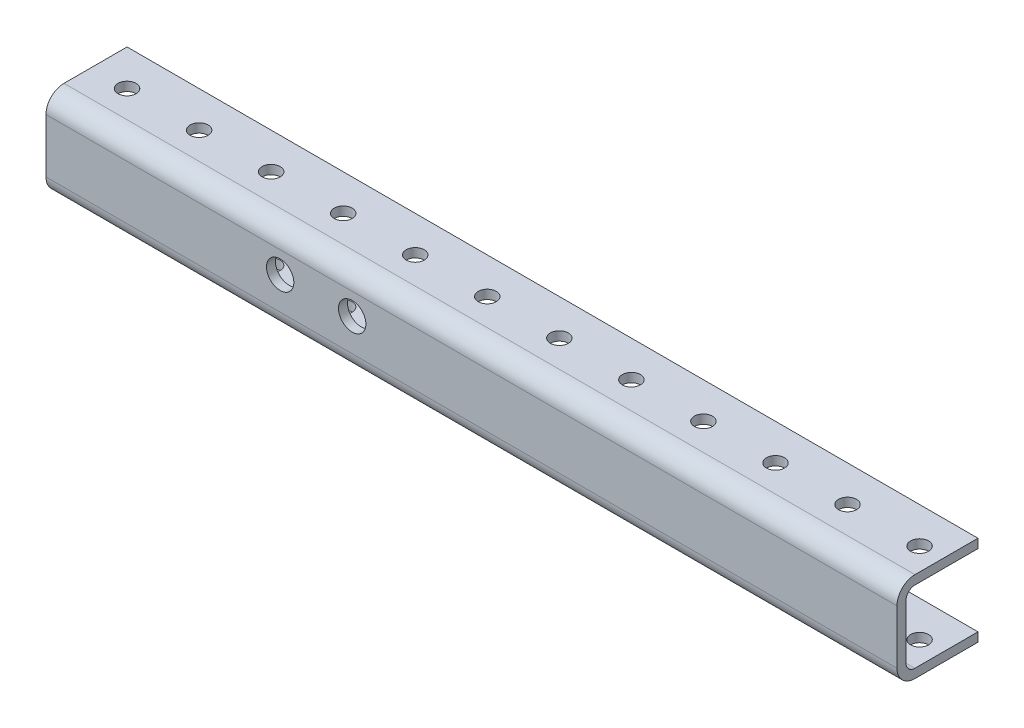
SolidWorks part; units mm, degrees
ref_plane "Front Plane" through (0, 0, 0) normal (0, 0, 1) x (1, 0, 0)
ref_plane "Top Plane" through (0, 0, 0) normal (0, 1, 0) x (1, 0, 0)
ref_plane "Right Plane" through (0, 0, 0) normal (1, 0, 0) x (0, 0, -1)
ref_plane "Plane1" through (0, 0, 3.175) normal (0, 0, 1) x (1, 0, 0)
sketch "Sketch1" plane through (0, 0, 3.175) normal (0, 0, 1) x (1, 0, 0)
  line L0 (872.98, -7.202) -> (872.98, 24.548)
  line L1 (872.98, 24.548) -> (-16.02, 24.548)
  line L2 (-16.02, 24.548) -> (-16.02, -7.202)
  line L3 (-16.02, -7.202) -> (872.98, -7.202)
extrude "Extrude1" add sketch "Sketch1" against normal blind 28.575
sketch "Sketch2" plane through (-16.02, 0, 0) normal (-1, 0, 0) x (0, 0, 1)
  line L0 (-25.4, 21.373) -> (-25.4, -4.027)
  line L1 (-25.4, -4.027) -> (0, -4.027)
  line L2 (0, -4.027) -> (0, 21.373)
  line L3 (0, 21.373) -> (-25.4, 21.373)
extrude "Extrude2" cut sketch "Sketch2" against normal up to next
hole_wizard "Hole1" positions "Sketch4" profile "Sketch3" legacy
sketch "Sketch4" plane through (0, 24.548, 0) normal (0, 1, 0) x (-1, 0, 0)
  point P0 (3.32, -12.7)
sketch "Sketch3" plane through (-3.32, 24.548, -12.7) normal (1, 0, 0) x (0, 0, 1)
  line L0 (0, 0) -> (0, 3.175)
  line L1 (0, 3.175) -> (3.175, 3.175)
  line L2 (3.175, 3.175) -> (3.175, 0)
  line L3 (3.175, 0) -> (0, 0)
  line L4 (0, 110) -> (0, -10) construction
  dimension "Diameter" = 6.35
  dimension "Depth" = 3.175
sketch3d "3DSketch1"
  point P0 (428.6664, 8.6668, -7.2024)
  point P1 (528.6664, 8.6668, -7.2024)
ref_axis "Axis1" through (528.6664, 8.6668, -7.2024) along (-1, 0, 0)
pattern_linear "LPattern1" count 35 spacing 25.4 along (1, 0, 0) of "Hole1"
hole_wizard "Hole2" positions "Sketch6" profile "Sketch5" legacy
sketch "Sketch6" plane through (0, 0, 3.175) normal (0, 0, 1) x (1, 0, 0)
  point P0 (66.53, 10.578)
sketch "Sketch5" plane through (66.53, 10.578, 3.175) normal (1, 0, 0) x (0, -1, 0)
  line L0 (0, 0) -> (0, 3.175)
  line L1 (0, 3.175) -> (4.826, 3.175)
  line L2 (4.826, 3.175) -> (4.826, 0)
  line L3 (4.826, 0) -> (0, 0)
  line L4 (0, 110) -> (0, -10) construction
  dimension "Diameter" = 9.652
  dimension "Depth" = 3.175
sketch3d "3DSketch2"
  point P0 (428.8468, 8.4517, -7.1294)
  point P1 (528.8468, 8.4517, -7.1294)
ref_axis "Axis2" through (528.8468, 8.4517, -7.1294) along (-1, 0, 0)
pattern_linear "LPattern2" count 12 spacing 25.4 along (1, 0, 0) skipping (2, 0), (3, 0), (4, 0), (5, 0), (6, 0), (7, 0), (8, 0), (9, 0) of "Hole2"
hole_wizard "Hole3" positions "Sketch8" profile "Sketch7" legacy
sketch "Sketch8" plane through (0, 0, 3.175) normal (0, 0, 1) x (1, 0, 0)
  point P0 (428.48, 6.768)
sketch "Sketch7" plane through (428.48, 6.768, 3.175) normal (1, 0, 0) x (0, -1, 0)
  line L0 (0, 0) -> (0, 3.175)
  line L1 (0, 3.175) -> (4.826, 3.175)
  line L2 (4.826, 3.175) -> (4.826, 0)
  line L3 (4.826, 0) -> (0, 0)
  line L4 (0, 110) -> (0, -10) construction
  dimension "Diameter" = 9.652
  dimension "Depth" = 3.175
hole_wizard "Hole4" positions "Sketch10" profile "Sketch9" legacy
sketch "Sketch10" plane through (0, 0, 3.175) normal (0, 0, 1) x (1, 0, 0)
  point P0 (511.03, 10.578)
sketch "Sketch9" plane through (511.03, 10.578, 3.175) normal (1, 0, 0) x (0, -1, 0)
  line L0 (0, 0) -> (0, 3.175)
  line L1 (0, 3.175) -> (4.826, 3.175)
  line L2 (4.826, 3.175) -> (4.826, 0)
  line L3 (4.826, 0) -> (0, 0)
  line L4 (0, 110) -> (0, -10) construction
  dimension "Diameter" = 9.652
  dimension "Depth" = 3.175
sketch3d "3DSketch3"
  point P0 (429.3014, 8.4448, -7.1738)
  point P1 (529.3014, 8.4448, -7.1738)
ref_axis "Axis3" through (529.3014, 8.4448, -7.1738) along (-1, 0, 0)
pattern_linear "LPattern3" count 12 spacing 25.4 along (1, 0, 0) skipping (2, 0), (3, 0), (4, 0), (5, 0), (6, 0), (7, 0), (8, 0), (9, 0) of "Hole4"
hole_wizard "Hole5" positions "Sketch12" profile "Sketch11" legacy
sketch "Sketch12" plane through (0, 0, 3.175) normal (0, 0, 1) x (1, 0, 0)
  point P0 (669.78, 8.673)
sketch "Sketch11" plane through (669.78, 8.673, 3.175) normal (1, 0, 0) x (0, -1, 0)
  line L0 (0, 0) -> (0, 3.175)
  line L1 (0, 3.175) -> (1.5875, 3.175)
  line L2 (1.5875, 3.175) -> (1.5875, 0)
  line L3 (1.5875, 0) -> (0, 0)
  line L4 (0, 110) -> (0, -10) construction
  dimension "Diameter" = 3.175
  dimension "Depth" = 3.175
hole_wizard "Hole6" positions "Sketch14" profile "Sketch13" legacy
sketch "Sketch14" plane through (0, -4.027, 0) normal (0, 1, 0) x (-1, 0, 0)
  point P0 (3.32, -12.7)
sketch "Sketch13" plane through (-3.32, -4.027, -12.7) normal (1, 0, 0) x (0, 0, 1)
  line L0 (0, 0) -> (0, 3.175)
  line L1 (0, 3.175) -> (3.175, 3.175)
  line L2 (3.175, 3.175) -> (3.175, 0)
  line L3 (3.175, 0) -> (0, 0)
  line L4 (0, 110) -> (0, -10) construction
  dimension "Diameter" = 6.35
  dimension "Depth" = 3.175
sketch3d "3DSketch4"
  point P0 (428.6444, 8.4444, -7.1991)
  point P1 (528.6444, 8.4444, -7.1991)
ref_axis "Axis4" through (528.6444, 8.4444, -7.1991) along (-1, 0, 0)
pattern_linear "LPattern4" count 35 spacing 25.4 along (1, 0, 0) of "Hole6"
fillet "Fillet1" radius 3.175 1 edges at (428.48, 21.373, 0) tangent propagation no
fillet "Fillet2" radius 3.175 1 edges at (428.48, -4.027, 0) tangent propagation no
fillet "Fillet3" radius 6.35 1 edges at (428.48, -7.202, 3.175) tangent propagation no
fillet "Fillet4" radius 6.35 1 edges at (428.48, 24.548, 3.175) tangent propagation no
sketch "Sketch15" plane through (0, 24.548, 0) normal (0, 1, 0) x (1, 0, 0)
  line L0 (-16.02, 25.4) -> (283.98, 25.4) construction
  line L1 (872.98, 25.4) -> (-16.02, 25.4) construction
  line L3 (283.98, 25.4) -> (880.1879, 25.4)
  line L4 (283.98, 25.4) -> (283.98, -15.2082)
  line L5 (283.98, -15.2082) -> (880.1879, -15.2082)
  line L6 (880.1879, 25.4) -> (880.1879, -15.2082)
  dimension "D1" = 300
extrude "Cut-Extrude1" cut sketch "Sketch15" against normal blind 77
